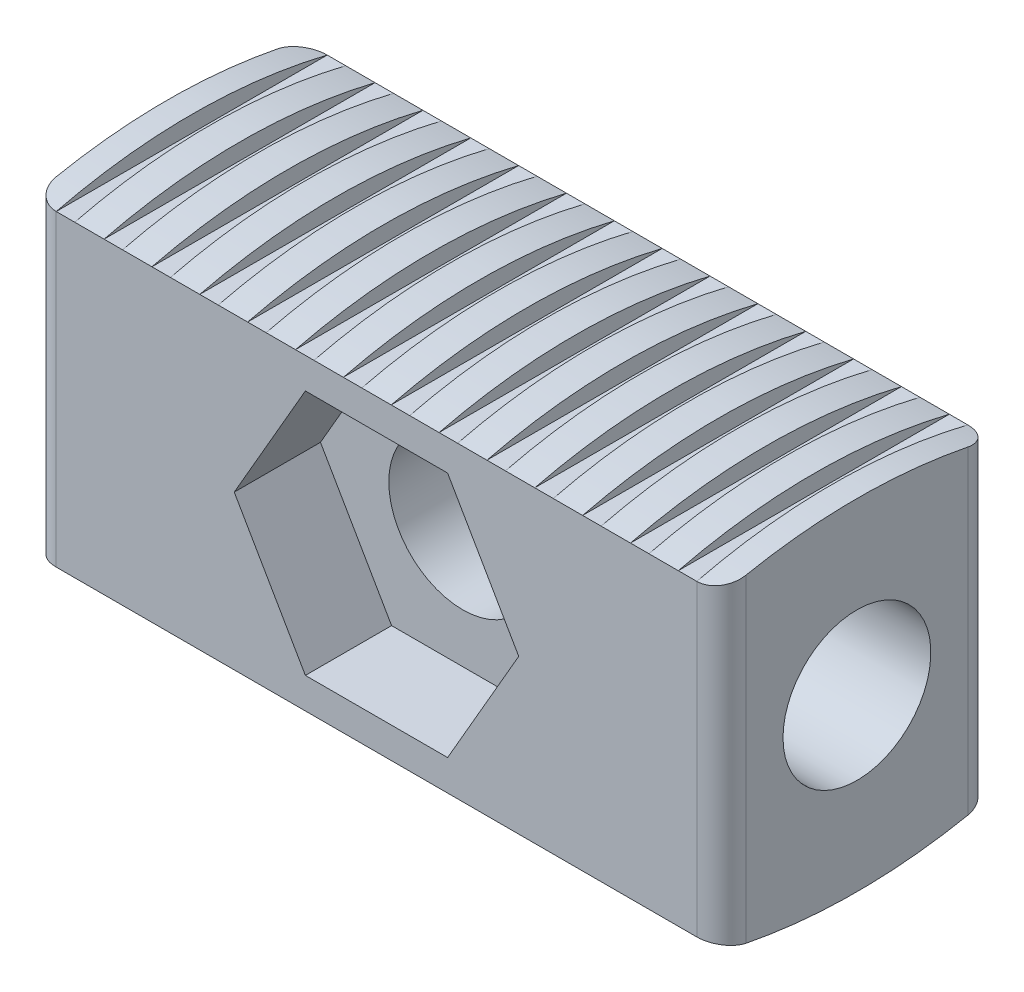
SolidWorks part; units mm, degrees
material "ABS"
ref_plane "Front Plane" through (0, 0, 0) normal (0, 0, 1) x (1, 0, 0)
ref_plane "Top Plane" through (0, 0, 0) normal (0, 1, 0) x (1, 0, 0)
ref_plane "Right Plane" through (0, 0, 0) normal (1, 0, 0) x (0, 0, -1)
sketch "Sketch1" plane through (0, 0, 0) normal (0, 0, 1) x (1, 0, 0)
  line L2 (2.8868, 5) -> (-2.8868, 5) construction
  line L3 (-2.8868, 5) -> (-5.7735, 0) construction
  line L4 (-5.7735, 0) -> (-2.8868, -5) construction
  line L5 (-2.8868, -5) -> (2.8868, -5) construction
  line L18 (0, 5) -> (0, -5) construction
  line L19 (0, 0) -> (0, -7.5) construction
  line L20 (5.7735, 0) -> (2.8868, 5) [skipped]
  line L21 (2.8868, -5) -> (5.7735, 0) [skipped]
  line L22 (-5.7735, 0) -> (-14, 0) construction
  line L23 (0, 5) -> (0, 7.5) construction
  line L24 (14, -7.5) -> (-14, -7.5)
  line L25 (-14, -7.5) -> (-14, 0)
  line L26 (-14, 0) -> (-14, 7.5)
  line L27 (-14, 7.5) -> (14, 7.5)
  line L28 (5.7735, 0) -> (14, 0) construction
  line L29 (14, 0) -> (14, 7.5)
  line L30 (14, -7.5) -> (14, 0)
  line L31 (5.7735, 0) -> (2.8868, -5) construction
  line L32 (2.8868, 5) -> (5.7735, 0) construction
  circle A0 centre (0, 0) radius 5 construction
  circle A2 centre (0, 0) radius 3
  dimension "D4" = 6
  dimension "D1" = 10
  dimension "D2" = 7.5
  dimension "D3" = 28
extrude "Boss-Extrude1" add sketch "Sketch1" along normal blind 11
sketch "Sketch3" plane through (0, 0, 11) normal (0, 0, 1) x (1, 0, 0)
  line L1 (5.7735, 0) -> (2.8868, 5)
  line L2 (2.8868, 5) -> (-2.8868, 5)
  line L3 (-2.8868, 5) -> (-5.7735, 0)
  line L4 (-5.7735, 0) -> (-2.8868, -5)
  line L5 (-2.8868, -5) -> (2.8868, -5)
  line L6 (2.8868, -5) -> (5.7735, 0)
  circle A0 centre (0, 0) radius 5 construction
  dimension "D1" = 10
extrude "Cut-Extrude3" cut sketch "Sketch3" against normal blind 3.5
ref_plane "Plane1" through (0, 0, 5.5) normal (0, 0, -1) x (-1, 0, 0)
sketch "Sketch6" plane through (0, -7.5, 0) normal (0, -1, 0) x (1, 0, 0)
  line L0 (-14, 11) -> (14, 11) construction
  line L1 (-13, 0) -> (-12.25, 0)
  line L2 (-13, 0) -> (-13, 11)
  line L3 (-13, 11) -> (-12.25, 11)
  line L4 (-12.25, 0) -> (-12.25, 11)
  line L5 (-14, 11) -> (-14, 0) construction
  line L6 (-11.0577, 0) -> (-11.0577, 11)
  line L7 (-11.0577, 0) -> (-10.3077, 0)
  line L8 (-10.3077, 0) -> (-10.3077, 11)
  line L9 (-11.0577, 11) -> (-10.3077, 11)
  line L10 (-9.1154, 0) -> (-9.1154, 11)
  line L11 (-9.1154, 0) -> (-8.3654, 0)
  line L12 (-8.3654, 0) -> (-8.3654, 11)
  line L13 (-9.1154, 11) -> (-8.3654, 11)
  line L14 (-7.1731, 0) -> (-7.1731, 11)
  line L15 (-7.1731, 0) -> (-6.4231, 0)
  line L16 (-6.4231, 0) -> (-6.4231, 11)
  line L17 (-7.1731, 11) -> (-6.4231, 11)
  line L18 (-5.2308, 0) -> (-5.2308, 11)
  line L19 (-5.2308, 0) -> (-4.4808, 0)
  line L20 (-4.4808, 0) -> (-4.4808, 11)
  line L21 (-5.2308, 11) -> (-4.4808, 11)
  line L22 (-3.2885, 0) -> (-3.2885, 11)
  line L23 (-3.2885, 0) -> (-2.5385, 0)
  line L24 (-2.5385, 0) -> (-2.5385, 11)
  line L25 (-3.2885, 11) -> (-2.5385, 11)
  line L26 (-1.3462, 0) -> (-1.3462, 11)
  line L27 (-1.3462, 0) -> (-0.5962, 0)
  line L28 (-0.5962, 0) -> (-0.5962, 11)
  line L29 (-1.3462, 11) -> (-0.5962, 11)
  line L30 (0.5962, 0) -> (0.5962, 11)
  line L31 (0.5962, 0) -> (1.3462, 0)
  line L32 (1.3462, 0) -> (1.3462, 11)
  line L33 (0.5962, 11) -> (1.3462, 11)
  line L34 (2.5385, 0) -> (2.5385, 11)
  line L35 (2.5385, 0) -> (3.2885, 0)
  line L36 (3.2885, 0) -> (3.2885, 11)
  line L37 (2.5385, 11) -> (3.2885, 11)
  line L38 (4.4808, 0) -> (4.4808, 11)
  line L39 (4.4808, 0) -> (5.2308, 0)
  line L40 (5.2308, 0) -> (5.2308, 11)
  line L41 (4.4808, 11) -> (5.2308, 11)
  line L42 (6.4231, 0) -> (6.4231, 11)
  line L43 (6.4231, 0) -> (7.1731, 0)
  line L44 (7.1731, 0) -> (7.1731, 11)
  line L45 (6.4231, 11) -> (7.1731, 11)
  line L46 (8.3654, 0) -> (8.3654, 11)
  line L47 (8.3654, 0) -> (9.1154, 0)
  line L48 (9.1154, 0) -> (9.1154, 11)
  line L49 (8.3654, 11) -> (9.1154, 11)
  line L50 (10.3077, 0) -> (10.3077, 11)
  line L51 (10.3077, 0) -> (11.0577, 0)
  line L52 (11.0577, 0) -> (11.0577, 11)
  line L53 (10.3077, 11) -> (11.0577, 11)
  line L54 (12.25, 0) -> (12.25, 11)
  line L55 (12.25, 0) -> (13, 0)
  line L56 (13, 0) -> (13, 11)
  line L57 (12.25, 11) -> (13, 11)
  line L62 (14, 11) -> (14, 0) construction
  dimension "D1" = 0.75
  dimension "D2" = 1
  dimension "D4" = 1
  dimension "D3" = 14
extrude "Cut-Extrude6" cut sketch "Sketch6" against normal blind 1.25
sketch "Sketch5" plane through (14, 0, 0) normal (1, 0, 0) x (0, 0, -1)
  line L0 (-11, -7.5) -> (0, -7.5) construction
  line L1 (-11, -7.5) -> (-11, 7.5) construction
  line L2 (0, -7.5) -> (0, 7.5) construction
  line L4 (-11, -6.25) -> (-11, -9.4486)
  line L5 (-11, -9.4486) -> (0, -9.4486)
  line L6 (0, -9.4486) -> (0, -6.25)
  arc A0 (-11, -6.25) -> (0, -6.25) centre (-5.5, 16.2114) ccw
  dimension "D1" = 1.25
extrude "Cut-Extrude5" cut sketch "Sketch5" against normal up to surface (28 mm away) up to face at (-14, 0, 5.5)
fillet "Fillet2" radius 1 4 edges at (14, 0.625, 0) (14, 0.625, 11) (-14, 0.625, 0) (-14, 0.625, 11)
mirror "Mirror3" about plane through (0, 0, 5.5) normal (0, 0, -1) of "Cut-Extrude3"
sketch "Sketch8" plane through (-14, 0, 0) normal (-1, 0, 0) x (0, 0, 1)
  line L0 (5.5, 0) -> (5.5, -9.7057) construction
  line L2 (0, 0) -> (5.5, 0) construction
  circle A0 centre (5.5, 0) radius 3
  dimension "D1" = 6
extrude "Cut-Extrude8" cut sketch "Sketch8" against normal blind 6
mirror "Mirror4" about plane through (0, 0, 0) normal (1, 0, 0) of "Cut-Extrude8"
mirror "Mirror5" about plane through (0, 0, 0) normal (0, 1, 0) of "Cut-Extrude5", "Cut-Extrude6"
